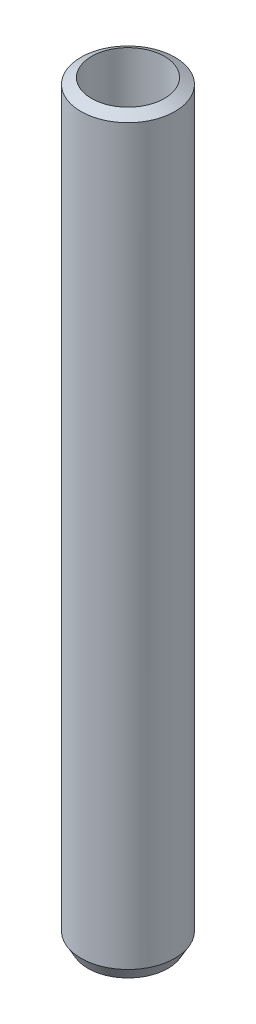
SolidWorks part; units mm, degrees
ref_plane "Front Plane" through (0, 0, 0) normal (0, 0, 1) x (1, 0, 0)
ref_plane "Top Plane" through (0, 0, 0) normal (0, 1, 0) x (1, 0, 0)
ref_plane "Right Plane" through (0, 0, 0) normal (1, 0, 0) x (0, 0, -1)
sketch "Sketch1" plane through (0, 0, 0) normal (0, 1, 0) x (1, 0, 0)
  circle A0 centre (0, 0) radius 37.5
  dimension "SHAFT_OD" = 75
extrude "Boss-Extrude1" add sketch "Sketch1" along normal blind 600
sketch "Sketch2" plane through (0, 0, 0) normal (0, 1, 0) x (1, 0, 0)
  circle A0 centre (0, 0) radius 29.0903
  dimension "BORE_D" = 58.1806
extrude "Cut-Extrude1" cut sketch "Sketch2" along normal through all
chamfer "Chamfer1" distance 5.5857 angle 60.37 2 edges at (0, 600, 37.5) (0, 0, 37.5) first distance on face at (0, 600, 37.5) first distance on face at (0, 0, 29.0903)
